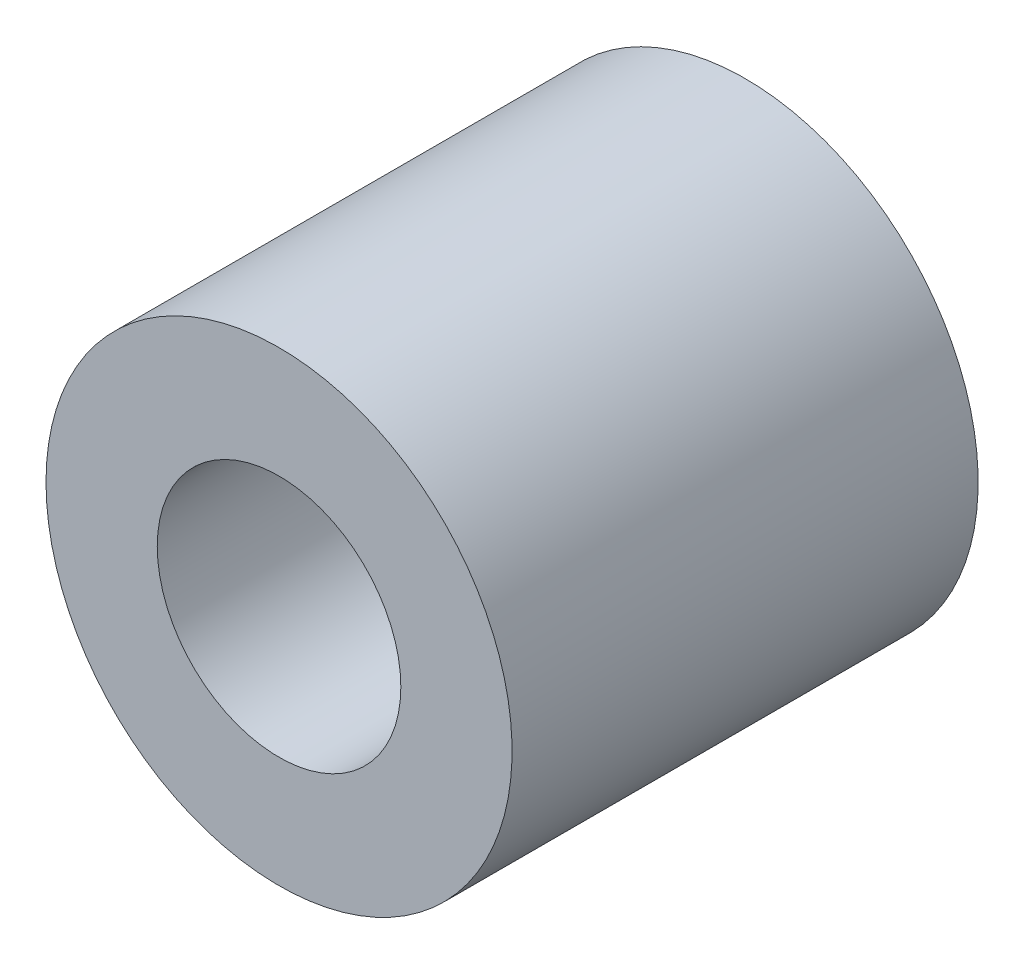
SolidWorks part; units mm, degrees
material "6061-T6 (SS)"
ref_plane "Front Plane" through (0, 0, 0) normal (0, 0, 1) x (1, 0, 0)
ref_plane "Top Plane" through (0, 0, 0) normal (0, 1, 0) x (1, 0, 0)
ref_plane "Right Plane" through (0, 0, 0) normal (1, 0, 0) x (0, 0, -1)
sketch "Sketch1" plane through (0, 0, 0) normal (0, 0, 1) x (1, 0, 0)
  circle A0 centre (0, 0) radius 2.4892
  circle A1 centre (0, 0) radius 4.7625
  dimension "D1" = 4.9784
  dimension "D2" = 9.525
extrude "Boss-Extrude1" add sketch "Sketch1" along normal blind 9.525
